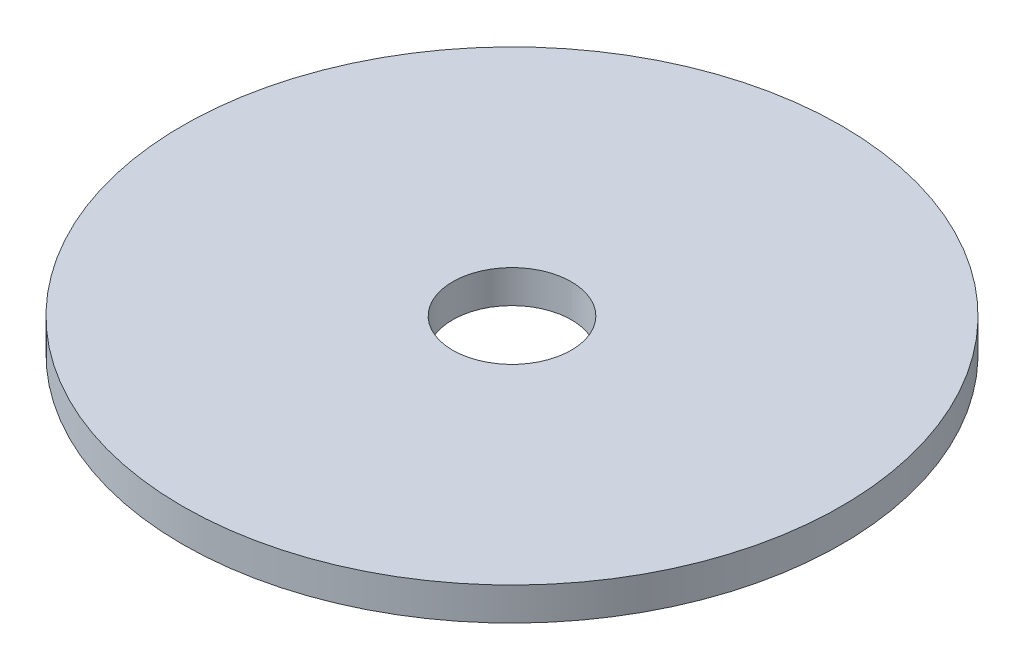
SolidWorks part; units mm, degrees
ref_plane "Front Plane" through (0, 0, 0) normal (0, 0, 1) x (1, 0, 0)
ref_plane "Top Plane" through (0, 0, 0) normal (0, 1, 0) x (1, 0, 0)
ref_plane "Right Plane" through (0, 0, 0) normal (1, 0, 0) x (0, 0, -1)
sketch "Sketch1" plane through (0, 0, 0) normal (0, 1, 0) x (1, 0, 0)
  line L0 (-2.75, -2.1651) -> (-1.9, -16.6)
  line L1 (1.9, -16.6) -> (2.75, -2.1651)
  line L2 (2.75, 2.1651) -> (1.9, 16.6)
  line L3 (-1.9, 16.6) -> (-2.75, 2.1651)
  line L4 (2.848, 2.202) -> (2, 16.603)
  line L5 (-2, 16.603) -> (-2.848, 2.202)
  line L6 (-2.848, -2.202) -> (-2, -16.603)
  line L7 (2, -16.603) -> (2.848, -2.202)
  arc A0 (-2.75, 2.1651) -> (-2.75, -2.1651) centre (0, 0) ccw
  arc A1 (-1.9, -16.6) -> (1.9, -16.6) centre (0, -16.6) ccw
  arc A2 (2.75, -2.1651) -> (3.5, 0) centre (0, 0) ccw
  arc A3 (3.5, 0) -> (2.75, 2.1651) centre (0, 0) ccw
  arc A4 (1.9, 16.6) -> (-1.9, 16.6) centre (0, 16.6) ccw
  arc A5 (2, 16.603) -> (-2, 16.603) centre (0, 16.6) ccw
  arc A6 (-2.848, 2.202) -> (-2.848, -2.202) centre (0, 0) ccw
  arc A7 (-2, -16.603) -> (2, -16.603) centre (0, -16.6) ccw
  arc A8 (2.848, -2.202) -> (3.6, 0) centre (0, 0) ccw
  arc A9 (3.6, 0) -> (2.848, 2.202) centre (0, 0) ccw
  circle A10 centre (0, 0) radius 20
  circle A11 centre (0, 0) radius 3.6
  dimension "D1" = 3.5
  dimension "D2" = 1.9
  dimension "D6" = 40
  dimension "D3" = 2.75
  dimension "D4" = 16.6
  dimension "D5" = 0.1
extrude "Boss-Extrude2" add sketch "Sketch1" along normal blind 2 contours A11 L1 A1 L0 L6 A7 L7 | A11 L0 A1 L1 | A11 L2 A4 L3 | A11 L4 A5 L5 L3 A4 L2 | A10 A9 A8 L7 A7 L6 A6 L5 A5 L4 region at (0, 0, 10.1891) region at (-2.3373, 0, 9.4685) region at (-2.8083, 0, -2.2801) region at (0, 0, -10.1891) region at (-19.4343, 0, 0)
